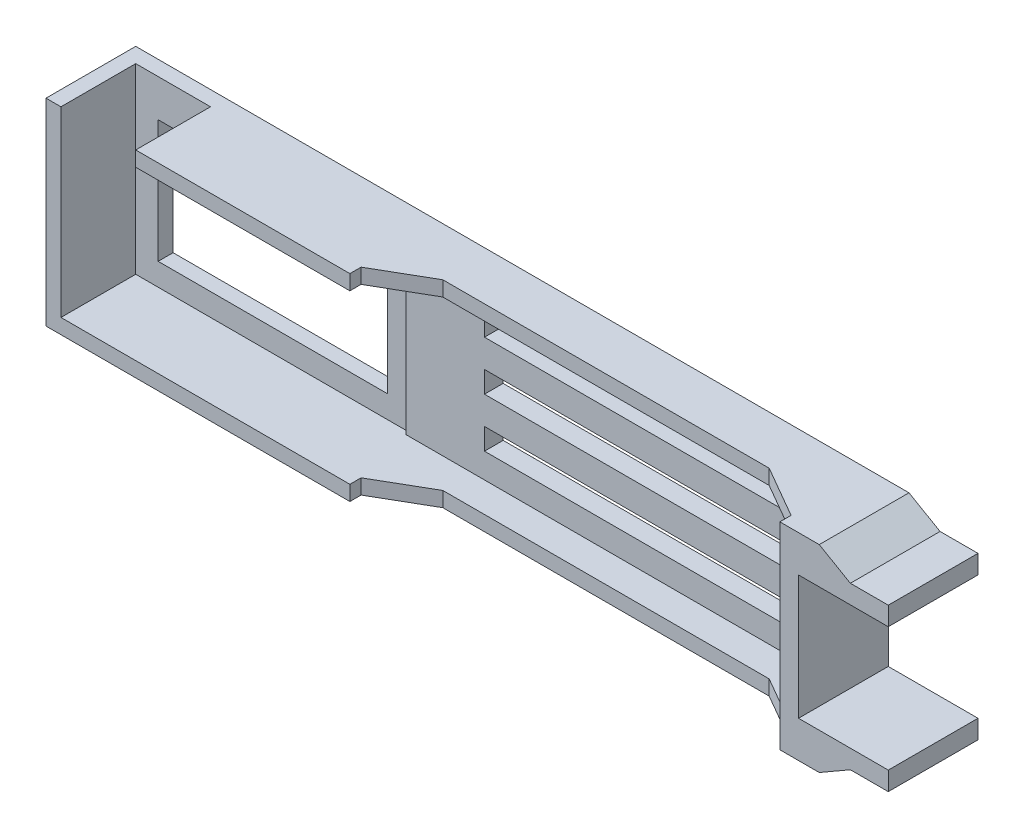
SolidWorks part; units mm, degrees
ref_plane "Plan de face" through (0, 0, 0) normal (0, 0, 1) x (1, 0, 0)
ref_plane "Plan de dessus" through (0, 0, 0) normal (0, 1, 0) x (1, 0, 0)
ref_plane "Plan de droite" through (0, 0, 0) normal (1, 0, 0) x (0, 0, -1)
sketch "Esquisse1" plane through (0, 0, 0) normal (0, 0, 1) x (1, 0, 0)
  line L1 (0, 0) -> (20.32, 0)
  line L2 (0, 0) -> (0, 13.2)
  line L3 (0, 13.2) -> (20.32, 13.2)
  line L4 (20.32, 0) -> (20.32, 13.2)
  dimension "D1" = 20.32
  dimension "D2" = 13.2
extrude "Boss.-Extru.1" add sketch "Esquisse1" along normal blind 6
sketch "Esquisse2" plane through (0, 0, 6) normal (0, 0, 1) x (1, 0, 0)
  line L0 (0, 13.2) -> (0, 0) construction
  line L1 (1, 1) -> (19.32, 1)
  line L2 (1, 1) -> (1, 12.2)
  line L3 (1, 12.2) -> (19.32, 12.2)
  line L4 (19.32, 1) -> (19.32, 12.2)
  line L5 (0, 0) -> (20.32, 0) construction
  line L6 (20.32, 13.2) -> (0, 13.2) construction
  line L7 (20.32, 0) -> (20.32, 13.2) construction
  dimension "D1" = 1
  dimension "D2" = 1
  dimension "D3" = 1
  dimension "D4" = 1
extrude "Enlèv. mat.-Extru.1" cut sketch "Esquisse2" against normal blind 5
sketch "Esquisse3" plane through (0, 0, 6) normal (0, 0, 1) x (1, 0, 0)
  line L0 (1, 12.2) -> (1, 1) construction
  line L1 (1, 12.2) -> (6, 12.2)
  line L2 (1, 12.2) -> (1, 13.2)
  line L3 (1, 13.2) -> (6, 13.2)
  line L4 (6, 12.2) -> (6, 13.2)
  line L5 (19.32, 12.2) -> (1, 12.2) construction
  line L6 (20.32, 13.2) -> (0, 13.2) construction
  dimension "D1" = 0
  dimension "D2" = 0
  dimension "D3" = 0
  dimension "D4" = 5
extrude "Enlèv. mat.-Extru.2" cut sketch "Esquisse3" against normal blind 5
sketch "Esquisse4" plane through (0, 0, 1) normal (0, 0, 1) x (1, 0, 0)
  line L0 (1, 13.2) -> (1, 1) construction
  line L1 (2.5, 10.7) -> (17.82, 10.7)
  line L2 (2.5, 10.7) -> (2.5, 2.5)
  line L3 (2.5, 2.5) -> (17.82, 2.5)
  line L4 (17.82, 10.7) -> (17.82, 2.5)
  line L5 (1, 1) -> (19.32, 1) construction
  line L6 (19.32, 1) -> (19.32, 12.2) construction
  line L7 (19.32, 12.2) -> (6, 12.2) construction
  dimension "D1" = 1.5
  dimension "D2" = 1.5
  dimension "D3" = 1.5
  dimension "D4" = 1.5
extrude "Enlèv. mat.-Extru.3" cut sketch "Esquisse4" against normal through all
sketch "Esquisse6" plane through (0, 0, 6) normal (0, 0, 1) x (1, 0, 0)
  line L0 (19.32, 12.2) -> (6, 12.2) construction
  line L1 (19.32, 12.2) -> (20.32, 12.2)
  line L2 (19.32, 12.2) -> (19.32, 1)
  line L3 (19.32, 1) -> (20.32, 1)
  line L4 (20.32, 12.2) -> (20.32, 1)
  line L5 (1, 1) -> (19.32, 1) construction
  line L6 (19.32, 1) -> (19.32, 12.2) construction
  line L7 (20.32, 0) -> (20.32, 13.2) construction
  dimension "D1" = 0
  dimension "D2" = 0
  dimension "D3" = 0
  dimension "D4" = 0
extrude "Enlèv. mat.-Extru.4" cut sketch "Esquisse6" against normal blind 4.75
sketch "Esquisse7" plane through (0, 0, 0) normal (0, 0, -1) x (-1, 0, 0)
  line L0 (-20.32, 0) -> (-20.32, 13.2) construction
  line L1 (-20.32, 13.2) -> (-50.32, 13.2)
  line L2 (-20.32, 13.2) -> (-20.32, 0)
  line L3 (-20.32, 0) -> (-50.32, 0)
  line L4 (-50.32, 13.2) -> (-50.32, 0)
  line L5 (-20.32, 13.2) -> (0, 13.2) construction
  line L6 (0, 0) -> (-20.32, 0) construction
  dimension "D1" = 0
  dimension "D2" = 0
  dimension "D3" = 0
  dimension "D4" = 30
extrude "Boss.-Extru.2" add sketch "Esquisse7" against normal blind 1.25
sketch "Esquisse8" plane through (0, 0, 1.25) normal (0, 0, 1) x (1, 0, 0)
  line L0 (20.32, 13.2) -> (50.32, 13.2) construction
  line L1 (49.07, 13.2) -> (50.32, 13.2)
  line L2 (49.07, 13.2) -> (49.07, 0)
  line L3 (49.07, 0) -> (50.32, 0)
  line L4 (50.32, 13.2) -> (50.32, 0)
  line L5 (50.32, 13.2) -> (50.32, 0) construction
  line L6 (50.32, 0) -> (20.32, 0) construction
  dimension "D1" = 0
  dimension "D2" = 0
  dimension "D3" = 1.25
  dimension "D4" = 0
extrude "Boss.-Extru.3" add sketch "Esquisse8" along normal blind 4.75
sketch "Esquisse9" plane through (50.32, 0, 0) normal (1, 0, 0) x (0, 0, -1)
  line L1 (-6, 12) -> (0, 12)
  line L2 (-6, 12) -> (-6, 10.75)
  line L3 (-6, 10.75) -> (0, 10.75)
  line L4 (0, 12) -> (0, 10.75)
  line L5 (-6, 0) -> (-6, 13.2) construction
  line L6 (0, 13.2) -> (0, 0) construction
  line L7 (-6, 0) -> (0, 0) construction
  line L8 (-6, 2.45) -> (0, 2.45)
  line L9 (-6, 2.45) -> (-6, 1.2)
  line L10 (-6, 1.2) -> (0, 1.2)
  line L11 (0, 2.45) -> (0, 1.2)
  line L12 (-6, 13.2) -> (0, 13.2) construction
  point P4 (0, 0)
  point P16 (0, 0)
  dimension "D1" = 1.2
  dimension "D2" = 0
  dimension "D3" = 0
  dimension "D4" = 1.25
  dimension "D5" = 1.2
  dimension "D6" = 0
  dimension "D7" = 0
  dimension "D8" = 1.25
  dimension "D9" = 8.3
extrude "Boss.-Extru.4" add sketch "Esquisse9" along normal blind 6
chamfer "Chanfrein1" distance 2 angle 60 2 edges at (50.32, 1.2, 3) (50.32, 12, 3) first distance on face at (50.32, 0.6, 3) first distance on face at (50.32, 12.6, 3)
sketch "Esquisse10" plane through (0, 0, 1.25) normal (0, 0, 1) x (1, 0, 0)
  line L0 (20.32, 12.2) -> (20.32, 13.2) construction
  line L1 (20.32, 13.2) -> (49.07, 13.2)
  line L2 (20.32, 13.2) -> (20.32, 12.2)
  line L3 (20.32, 12.2) -> (49.07, 12.2)
  line L4 (49.07, 13.2) -> (49.07, 12.2)
  line L5 (49.07, 13.2) -> (49.07, 0) construction
  line L6 (20.32, 13.2) -> (6, 13.2) construction
  line L7 (20.32, 1) -> (49.07, 1)
  line L8 (20.32, 1) -> (20.32, 0)
  line L9 (20.32, 0) -> (49.07, 0)
  line L10 (49.07, 1) -> (49.07, 0)
  line L11 (49.07, 0) -> (20.32, 0) construction
  line L12 (20.32, 0) -> (20.32, 1) construction
  dimension "D1" = 1
  dimension "D2" = 0
  dimension "D3" = 0
  dimension "D4" = 0
  dimension "D5" = 0
  dimension "D6" = 0
  dimension "D7" = 0
extrude "Boss.-Extru.5" add sketch "Esquisse10" along normal blind 2
chamfer "Chanfrein2" distance 2 angle 60 4 edges at (49.07, 0.5, 3.25) (49.07, 12.7, 3.25) (20.32, 0.5, 3.25) (20.32, 12.7, 3.25) first distance on face at (49.07, 6.6, 3.4375) first distance on face at (20.32, 0.5, 4.625) first distance on face at (20.32, 12.7, 4.625)
sketch "Esquisse11" plane through (0, 0, 1.25) normal (0, 0, 1) x (1, 0, 0)
  line L0 (49.07, 12.2) -> (19.32, 12.2) construction
  line L1 (24.57, 10.7) -> (45.57, 10.7)
  line L2 (24.57, 10.7) -> (24.57, 9.2665)
  line L3 (24.57, 9.2665) -> (45.57, 9.2665)
  line L4 (45.57, 10.7) -> (45.57, 9.2665)
  line L5 (49.07, 12.2) -> (49.07, 1) construction
  line L6 (24.57, 7.4) -> (24.57, 5.9665)
  line L7 (24.57, 7.4) -> (45.57, 7.4)
  line L8 (45.57, 7.4) -> (45.57, 5.9665)
  line L9 (24.57, 5.9665) -> (45.57, 5.9665)
  line L10 (24.57, 4.1) -> (24.57, 2.6665)
  line L11 (24.57, 4.1) -> (45.57, 4.1)
  line L12 (45.57, 4.1) -> (45.57, 2.6665)
  line L13 (24.57, 2.6665) -> (45.57, 2.6665)
  dimension "D1" = 1.5
  dimension "D2" = 21
  dimension "D3" = 3.5
  dimension "D4" = 3
extrude "Enlèv. mat.-Extru.5" cut sketch "Esquisse11" against normal blind 2
